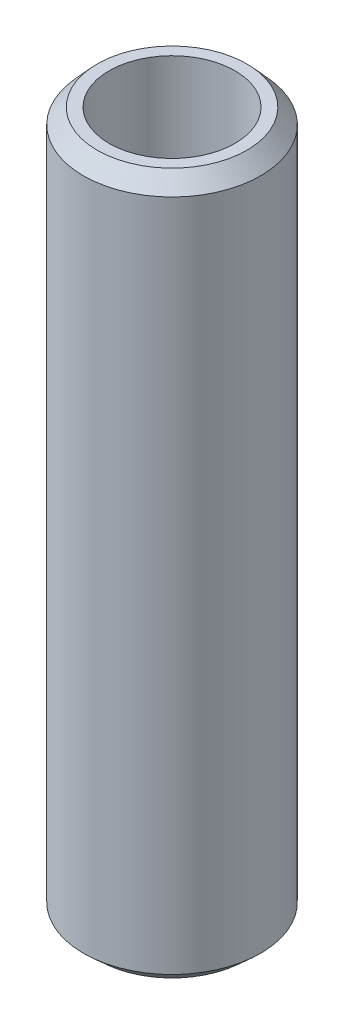
SolidWorks part; units mm, degrees
ref_plane "Front Plane" through (0, 0, 0) normal (0, 0, 1) x (1, 0, 0)
ref_plane "Top Plane" through (0, 0, 0) normal (0, 1, 0) x (1, 0, 0)
ref_plane "Right Plane" through (0, 0, 0) normal (1, 0, 0) x (0, 0, -1)
sketch "Sketch1" plane through (0, 0, 0) normal (0, 1, 0) x (1, 0, 0)
  circle A0 centre (0, 0) radius 25
  dimension "SHAFT_OD" = 50
extrude "Boss-Extrude1" add sketch "Sketch1" along normal blind 198.1147
sketch "Sketch2" plane through (0, 0, 0) normal (0, 1, 0) x (1, 0, 0)
  circle A0 centre (0, 0) radius 17.7572
  dimension "BORE_D" = 35.5145
extrude "Cut-Extrude1" cut sketch "Sketch2" along normal through all
chamfer "Chamfer1" distance 4.2926 angle 42.211 2 edges at (0, 198.1147, 25) (0, 0, 25) first distance on face at (0, 198.1147, 25) first distance on face at (0, 0, 17.7572)
